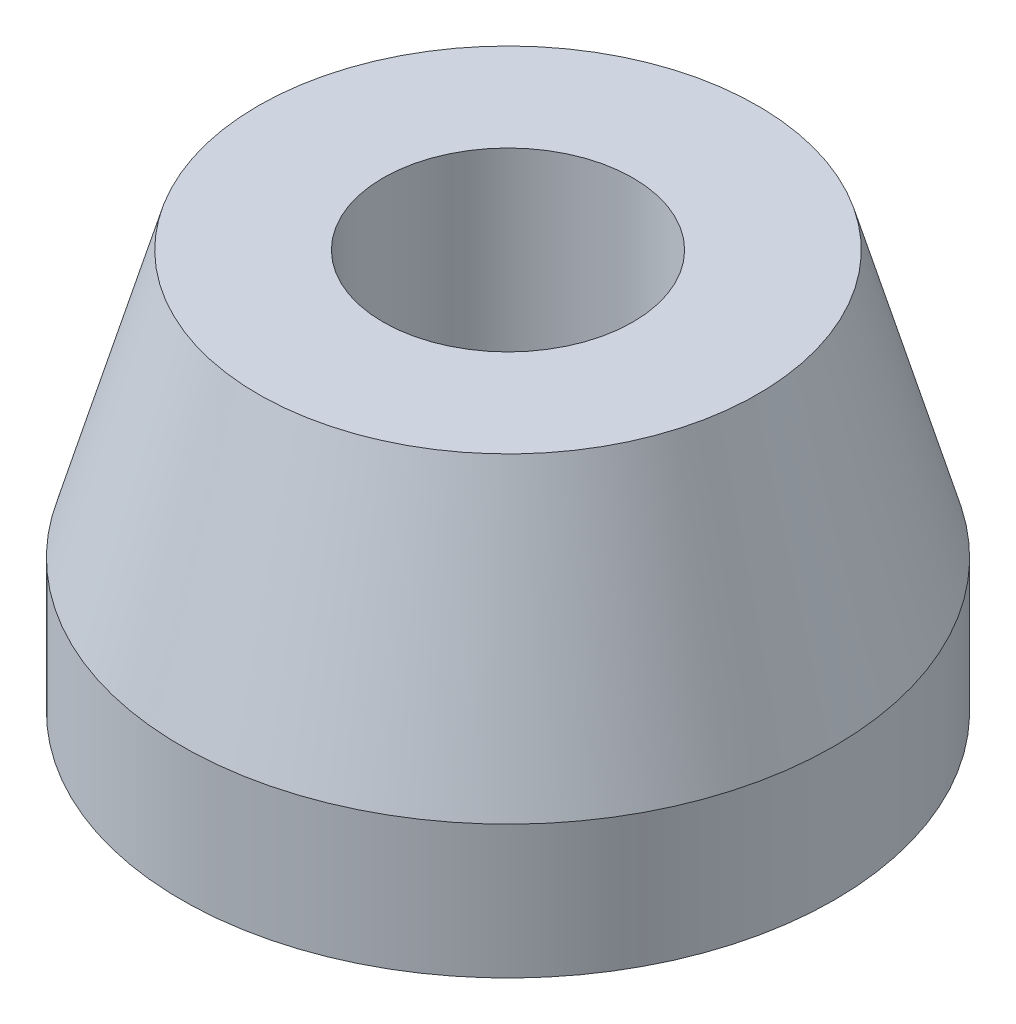
SolidWorks part; units mm, degrees
ref_plane "Front Plane" through (0, 0, 0) normal (0, 0, 1) x (1, 0, 0)
ref_plane "Top Plane" through (0, 0, 0) normal (0, 1, 0) x (1, 0, 0)
ref_plane "Right Plane" through (0, 0, 0) normal (1, 0, 0) x (0, 0, -1)
sketch "Sketch1" plane through (0, 0, 0) normal (0, 0, 1) x (1, 0, 0)
  line L0 (0, 0) -> (-12.446, 0)
  line L1 (-12.446, 0) -> (-12.446, 5.08)
  line L2 (-12.446, 5.08) -> (-9.525, 15.24)
  line L3 (-9.525, 15.24) -> (0, 15.24)
  line L4 (0, 15.24) -> (0, 0)
  dimension "D1" = 5.08
  dimension "D2" = 15.24
  dimension "D3" = 9.525
  dimension "D4" = 12.446
revolve "Revolve1" add sketch "Sketch1" angle 360 about L4
sketch "Sketch2" plane through (0, 15.24, 0) normal (0, 1, 0) x (1, 0, 0)
  circle A0 centre (0, 0) radius 4.7625
  dimension "D1" = 9.525
extrude "Cut-Extrude1" cut sketch "Sketch2" against normal through all both and the other way through all
equation "\"OldSchoolLengthHoles\"= 2.5in'OldSchool > NewSchool"
equation "\"SchoolWidthHoles\"= 1.625in'OldSchool = NewSchool"
equation "\"Angle\"= 40deg'Looks about <= 40deg"
equation "\"Width\"= 2.125in'Pretty sure this is standardized on longboard and skateboard"
equation "\"Length\"= 3in'Will have some variation?"
equation "\"NewSchoolLengthHoles\"= 2.125in'NewSchool Mounting"
equation "\"HoleSize\"= ( 3in / 16 )'hole"
equation "\"Depth\"= 1in / 8'Assuming same depth as a riserplate"
equation "\"KingpinBoltSize\"= 3in / 8"
equation "\"PivotCupDia\"= 0.63in'0.7in (large) 0.626 (small)"
equation "\"PivotCupDepth\"= 12mm'15mm (large) 12mm (small)"
equation "\"PivotCupEndAngle\"= 21.4' Assuming it is indy pivots"
equation "\"PivotCupInnerDia\"= 0.43in'0.5in (large) 0.43 (small)"
equation "\"BushingDia\"= .98in"
equation "\"BusingDepth\"= .6in"
equation "\"BushingSmallDia\"= .75in"
equation "\"D1@Sketch1\"=\"BusingDepth\"/3"
equation "\"D2@Sketch1\"=\"BusingDepth\""
equation "\"D3@Sketch1\"=\"BushingSmallDia\"/2"
equation "\"D4@Sketch1\"=\"BushingDia\"/2"
equation "\"D1@Sketch2\"=\"KingpinBoltSize\""
